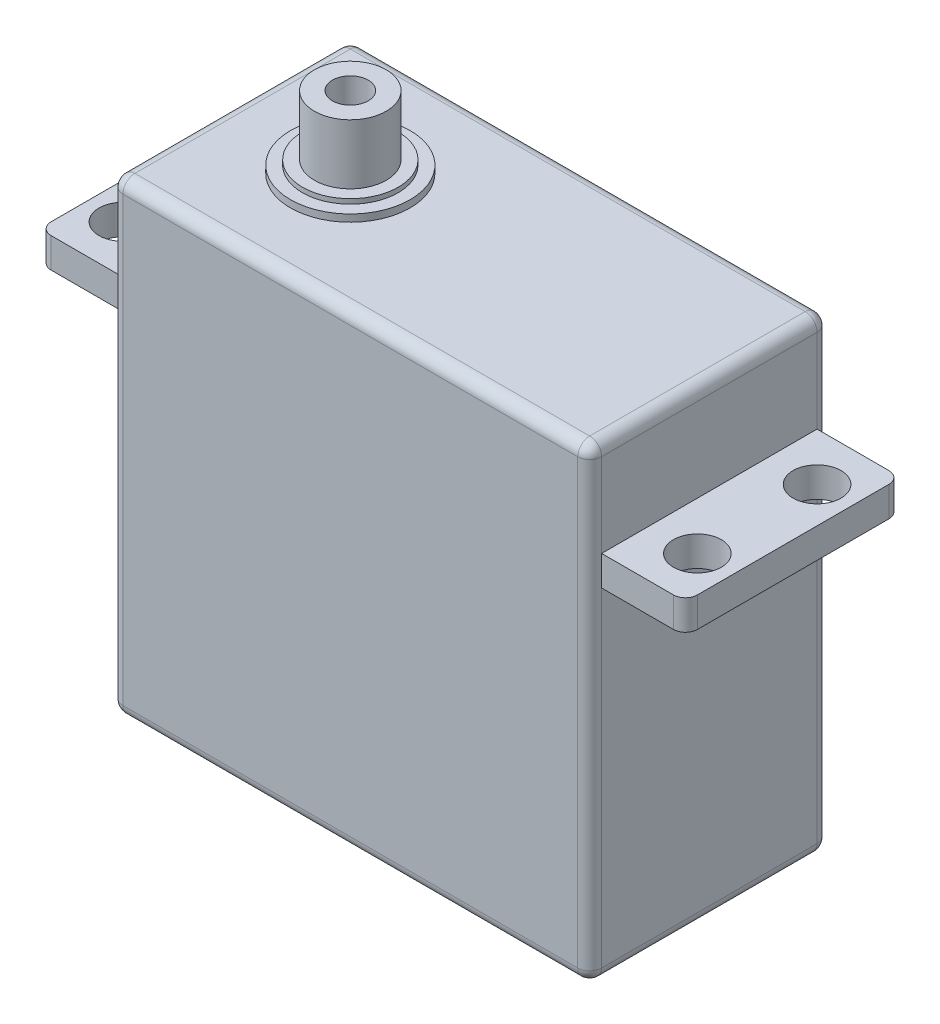
SolidWorks part; units mm, degrees
ref_plane "前视基准面" through (0, 0, 0) normal (0, 0, 1) x (1, 0, 0)
ref_plane "上视基准面" through (0, 0, 0) normal (0, 1, 0) x (1, 0, 0)
ref_plane "右视基准面" through (0, 0, 0) normal (1, 0, 0) x (0, 0, -1)
other "Configuration Table"
sketch "草图2" plane through (0, 0, 0) normal (0, 0, 1) x (1, 0, 0)
  line L1 (-39.1028, 55.0386) -> (0.8972, 55.0386)
  line L2 (-39.1028, 55.0386) -> (-39.1028, 16.0386)
  line L3 (-39.1028, 16.0386) -> (0.8972, 16.0386)
  line L4 (0.8972, 55.0386) -> (0.8972, 16.0386)
  dimension "D1" = 39
  dimension "D2" = 40
extrude "凸台-拉伸1" add sketch "草图2" along normal blind 20
fillet "圆角1" radius 1 12 edges at (0.8972, 55.0386, 10) (-19.1028, 55.0386, 0) (-39.1028, 55.0386, 10) (-39.1028, 35.5386, 0) (-39.1028, 16.0386, 10) (-19.1028, 16.0386, 0) (0.8972, 35.5386, 0) (0.8972, 16.0386, 10) (-19.1028, 16.0386, 20) (0.8972, 35.5386, 20) (-19.1028, 55.0386, 20) (-39.1028, 35.5386, 20)
sketch "草图4" plane through (0, 55.0386, 0) normal (0, 1, 0) x (1, 0, 0)
  circle A0 centre (-29.1028, -10) radius 3
  point P5 (0, 0)
extrude "凸台-拉伸2" add sketch "草图4" along normal blind 6 separate body
sketch "草图5" plane through (0.8972, 0, 0) normal (1, 0, 0) x (0, 0, -1)
  line L1 (-1, 17.0386) -> (-1, 54.0386) construction
  line L2 (-1, 47.0386) -> (-19, 47.0386)
  line L4 (-19, 47.0386) -> (-19, 44.5386)
  line L5 (-19, 54.0386) -> (-19, 17.0386) construction
  line L6 (-19, 44.5386) -> (-1, 44.5386)
  line L7 (-1, 44.5386) -> (-1, 47.0386)
  point P6 (-1, 34.848)
  dimension "D2" = 18
  dimension "D3" = 2.5
  dimension "D4" = 18
  dimension "D5" = 2.5
extrude "凸台-拉伸3" add sketch "草图5" along normal blind 7
sketch "草图7" plane through (-39.1028, 0, 0) normal (-1, 0, 0) x (0, 0, 1)
  line L1 (19, 17.0386) -> (19, 54.0386) construction
  line L2 (19, 47.0386) -> (1, 47.0386)
  line L4 (1, 47.0386) -> (1, 44.5386)
  line L5 (1, 54.0386) -> (1, 17.0386) construction
  line L6 (1, 44.5386) -> (19, 44.5386)
  line L7 (19, 44.5386) -> (19, 47.0386)
  dimension "D2" = 18
  dimension "D3" = 2.5
  dimension "D4" = 18
  dimension "D5" = 2.5
extrude "凸台-拉伸4" add sketch "草图7" along normal blind 7
sketch "草图8" plane through (0, 47.0386, 0) normal (0, 1, 0) x (1, 0, 0)
  circle A0 centre (-43.1028, -5) radius 2
  circle A1 centre (-43.1028, -15) radius 2
  circle A2 centre (4.8972, -5) radius 2
  circle A3 centre (4.8972, -15) radius 2
  dimension "D3" = 10
  dimension "D4" = 10
extrude "切除-拉伸1" cut sketch "草图8" against normal blind 7 contours A0 | A1 | A2 | A3
fillet "圆角2" radius 1 4 edges at (7.8972, 45.7886, 19) (7.8972, 45.7886, 1) (-46.1028, 45.7886, 19) (-46.1028, 45.7886, 1)
sketch "草图12" plane through (0, 61.0386, 0) normal (0, 1, 0) x (1, 0, 0)
  circle A2 centre (-29.1028, -10) radius 1.5
extrude "切除-拉伸2" cut sketch "草图12" against normal blind 7
sketch "草图13" plane through (0, 55.0386, 0) normal (0, 1, 0) x (1, 0, 0)
  circle A0 centre (-29.1028, -10) radius 4
  point P3 (0, 0)
extrude "凸台-拉伸5" add sketch "草图13" along normal blind 1
sketch "草图14" plane through (0, 55.0386, 0) normal (0, 1, 0) x (1, 0, 0)
  circle A0 centre (-29.1028, -10) radius 5
extrude "凸台-拉伸6" add sketch "草图14" along normal blind 0.6
sketch "草图15" plane through (0, 56.0386, 0) normal (0, 1, 0) x (1, 0, 0)
  circle A1 centre (-29.1028, -10) radius 1.5
  circle A2 centre (-29.1028, -10) radius 1.5
  dimension "D1" = 0
extrude "切除-拉伸3" cut sketch "草图15" against normal up to next
